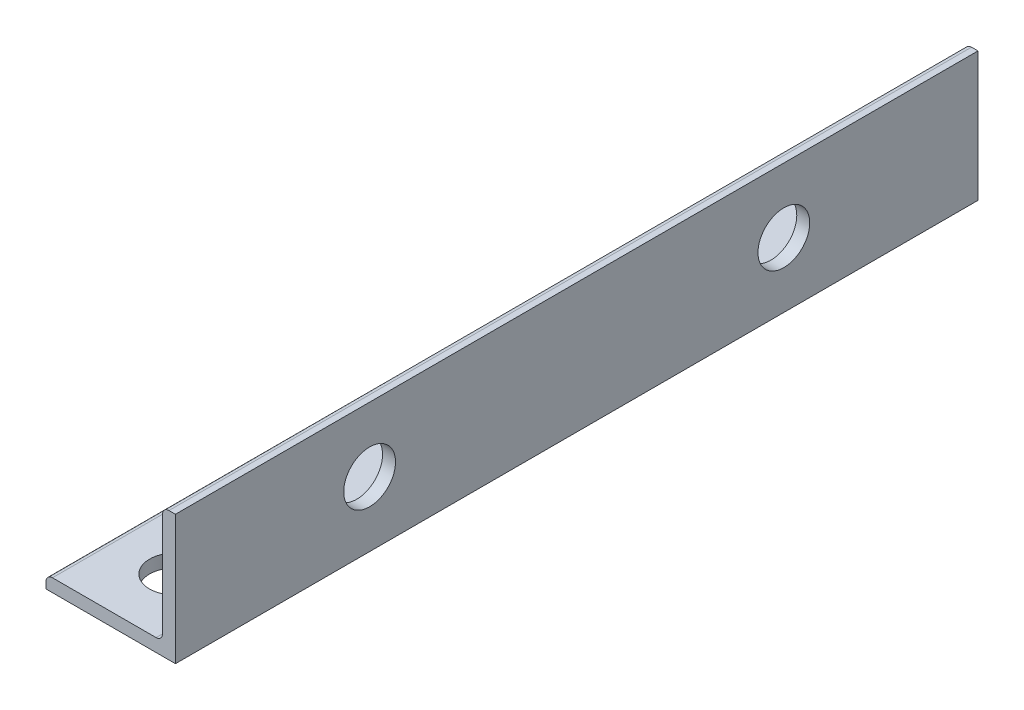
SolidWorks part; units mm, degrees
ref_plane "Front Plane" through (0, 0, 0) normal (0, 0, 1) x (1, 0, 0)
ref_plane "Top Plane" through (0, 0, 0) normal (0, 1, 0) x (1, 0, 0)
ref_plane "Right Plane" through (0, 0, 0) normal (1, 0, 0) x (0, 0, -1)
sketch "Sketch2" plane through (0, 0, 0) normal (0, 0, 1) x (1, 0, 0)
  line L0 (-7.9375, 0) -> (7.9375, 0)
  line L1 (7.9375, 0) -> (7.9375, 15.875)
  line L2 (7.9375, 15.875) -> (6.35, 15.875) construction
  line L3 (6.35, 15.0813) -> (6.35, 2.3812)
  line L4 (5.5563, 1.5875) -> (-7.1438, 1.5875)
  line L5 (-7.9375, 0) -> (-7.9375, 1.5875) construction
  line L6 (7.1438, 15.875) -> (7.9375, 15.875)
  line L7 (-7.9375, 0.7937) -> (-7.9375, 0)
  arc A0 (6.35, 15.0813) -> (7.1438, 15.875) centre (7.1438, 15.0813) cw
  arc A1 (-7.9375, 0.7937) -> (-7.1438, 1.5875) centre (-7.1438, 0.7937) cw
  arc A2 (6.35, 2.3812) -> (5.5563, 1.5875) centre (5.5563, 2.3812) cw
  dimension "Vert" = 15.875
  dimension "Horz" = 15.875
  dimension "Thickness" = 1.5875
extrude "Boss-Extrude1" add sketch "Sketch2" along normal mid plane 98.425
ref_plane "Contact Plane 1" through (0, 1.5875, 0) normal (0, 1, 0) x (1, 0, 0)
ref_plane "Contact Plane 2" through (6.35, 0, 0) normal (-1, 0, 0) x (0, 0, 1)
sketch "Sketch3" plane through (7.9375, 0, 0) normal (1, 0, 0) x (0, 0, -1)
  line L0 (25.4, 7.9375) -> (-25.4, 7.9375)
  line L1 (-49.2125, 15.875) -> (49.2125, 15.875) construction
  line L2 (-49.2125, 15.875) -> (-49.2125, 0) construction
  line L3 (-49.2125, 0) -> (49.2125, 0) construction
  line L4 (49.2125, 15.875) -> (49.2125, 0) construction
  circle A0 centre (-25.4, 7.9375) radius 3.175
  circle A1 centre (25.4, 7.9375) radius 3.175
  point P6 (49.2125, 7.9375)
  point P10 (0, 15.875)
  point P13 (0, 7.9375)
  dimension "D1" = 6.35
  dimension "D2" = 50.8
extrude "Cut-Extrude1" cut sketch "Sketch3" against normal through all contours A0 | A1 region at (7.9375, 7.9375, 28.4852) region at (7.9375, 11.0227, -25.4)
sketch "Sketch4" plane through (0, 0, 0) normal (0, -1, 0) x (1, 0, 0)
  line L0 (0, 41.275) -> (0, -41.275) construction
  line L1 (-7.9375, -49.2125) -> (7.9375, -49.2125) construction
  line L3 (7.9375, 49.2125) -> (7.9375, -49.2125) construction
  line L4 (0, 41.275) -> (7.9375, 41.275) construction
  line L6 (0, 41.275) -> (0, 49.2125) construction
  line L7 (-7.9375, 49.2125) -> (7.9375, 49.2125) construction
  circle A0 centre (0, -41.275) radius 3.175
  circle A1 centre (0, 41.275) radius 3.175
  point P4 (0, 0)
  point P9 (0, -49.2125)
  point P14 (7.9375, 0)
  dimension "D1" = 6.35
extrude "Cut-Extrude2" cut sketch "Sketch4" against normal up to next
